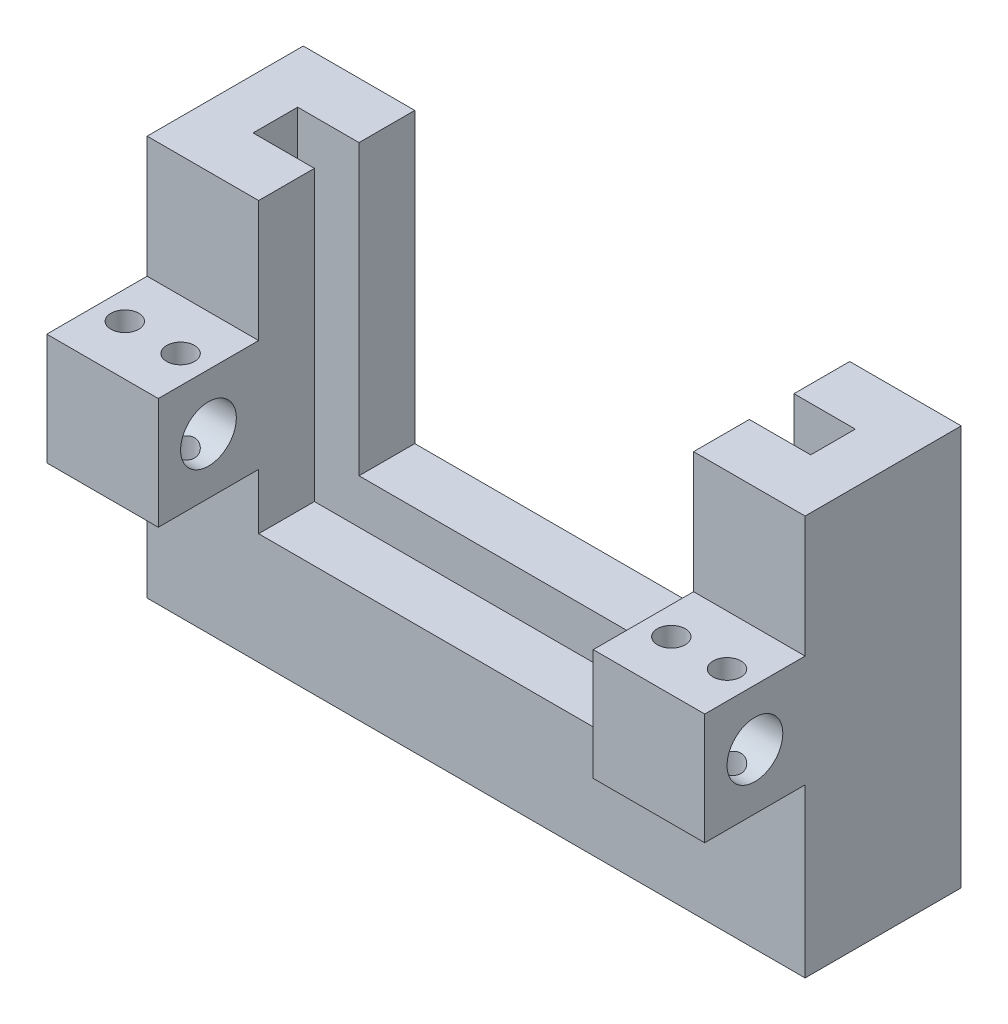
SolidWorks part; units mm, degrees
material "PVC Rigid"
ref_plane "Front Plane" through (0, 0, 0) normal (0, 0, 1) x (1, 0, 0)
ref_plane "Top Plane" through (0, 0, 0) normal (0, 1, 0) x (1, 0, 0)
ref_plane "Right Plane" through (0, 0, 0) normal (1, 0, 0) x (0, 0, -1)
sketch "Sketch3" plane through (0, 0, 0) normal (0, 0, 1) x (1, 0, 0)
  line L0 (-78, 63.5) -> (-78, -40)
  line L1 (118, -80) -> (-118, -80)
  line L2 (118, -80) -> (118, 63.5)
  line L3 (118, 63.5) -> (78, 63.5)
  line L4 (-118, -80) -> (-118, 63.5)
  line L8 (-78, -40) -> (78, -40)
  line L9 (78, 63.5) -> (78, -40)
  line L10 (-78, 63.5) -> (-118, 63.5)
  point P0 (0, 0)
extrude "Boss-Extrude1" add sketch "Sketch3" along normal blind 56 contours L0 L8 L9 L3 L2 L1 L4 L10
sketch "Sketch4" plane through (0, 0, 0) normal (0, 1, 0) x (1, 0, 0)
  line L1 (100, -20) -> (-100, -20)
  line L2 (100, -20) -> (100, -36)
  line L3 (100, -36) -> (-100, -36)
  line L4 (-100, -20) -> (-100, -36)
extrude "Cut-Extrude2" cut sketch "Sketch4" along normal through all and the other way offset from surface 20 contours L1 L4 L3 L2 other way up to face at (0, -80, 28)
sketch "Sketch6" plane through (0, 0, 56) normal (0, 0, 1) x (1, 0, 0)
  line L0 (118, -80) -> (118, 63.5) construction
  line L1 (-118, 20) -> (-78, 20)
  line L2 (-118, 20) -> (-118, -20)
  line L3 (-118, -20) -> (-78, -20)
  line L4 (118, 20) -> (118, -20)
  line L9 (-78, 20) -> (-78, -20)
  line L11 (78, 20) -> (78, -20)
  line L14 (78, -20) -> (118, -20)
  line L17 (78, 20) -> (118, 20)
  point P0 (0, 0)
  point P8 (0, 0)
extrude "Boss-Extrude2" add sketch "Sketch6" along normal blind 36 contours L17 L4 L14 L11 | L1 L9 L3 L2
sketch "Sketch7" plane through (118, 0, 0) normal (1, 0, 0) x (0, 0, -1)
  circle A0 centre (-74, 0) radius 10
extrude "Cut-Extrude3" cut sketch "Sketch7" against normal blind 260
sketch "Sketch8" plane through (0, 20, 0) normal (0, 1, 0) x (1, 0, 0)
  line L2 (0, 0) -> (0, -125) construction
  circle A0 centre (88, -74) radius 5
  circle A1 centre (108, -74) radius 5
  circle A2 centre (-88, -74) radius 5
  circle A3 centre (-108, -74) radius 5
  dimension "D1" = 2
extrude "Cut-Extrude4" cut sketch "Sketch8" against normal through all
